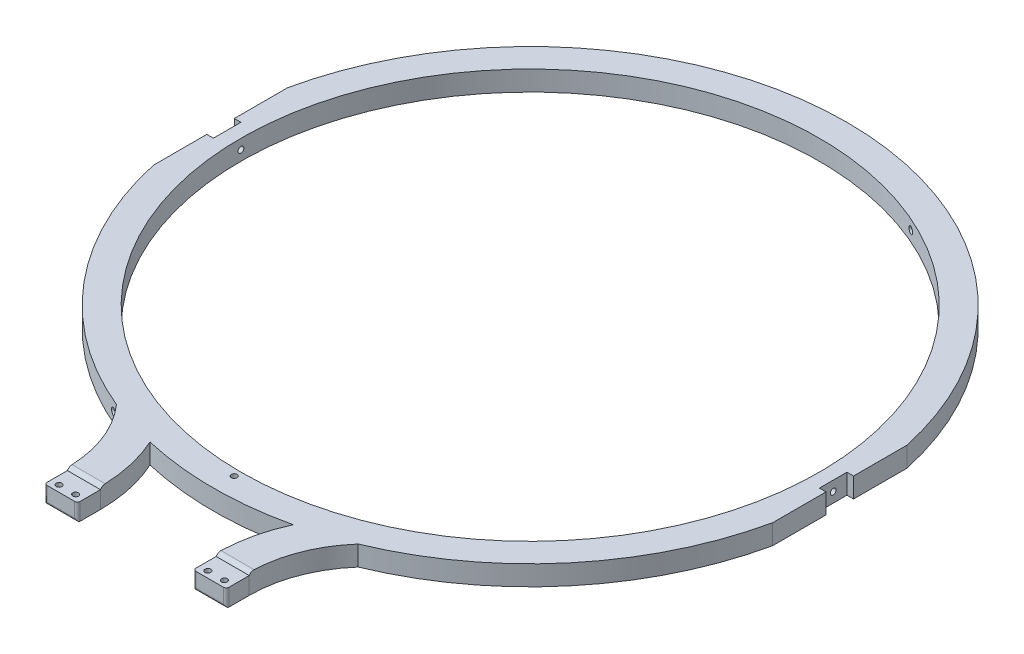
SolidWorks part; units mm, degrees
ref_plane "Front Plane" through (0, 0, 0) normal (0, 0, 1) x (1, 0, 0)
ref_plane "Top Plane" through (0, 0, 0) normal (0, 1, 0) x (1, 0, 0)
ref_plane "Right Plane" through (0, 0, 0) normal (1, 0, 0) x (0, 0, -1)
sketch "Sketch2" plane through (0, 0, 0) normal (0, 1, 0) x (1, 0, 0)
  line L0 (0, -135) -> (0, -115) construction
  line L1 (0, -135) -> (-21, -135) construction
  line L4 (-8.75, -110) -> (8.75, -110) construction
  line L6 (0, -135) -> (21, -135) construction
  line L8 (0, -115) -> (0, -105) construction
  line L11 (-33, -135) -> (-33, -143.35)
  line L12 (-33, -143.35) -> (-21, -143.35)
  line L13 (-21, -135) -> (-21, -143.35)
  line L15 (21, -135) -> (21, -143.35)
  line L16 (21, -143.35) -> (33, -143.35)
  line L17 (33, -135) -> (33, -143.35)
  arc A0 (-26, -112.0223) -> (26, -112.0223) centre (0, 0) ccw
  circle A1 centre (0, 0) radius 105
  arc A5 (-21, -135) -> (-26, -112.0223) centre (-76.2974, -135) ccw
  arc A6 (-33, -135) -> (-43.8788, -106.2998) centre (-76.2974, -135) ccw
  arc A7 (26, -112.0223) -> (21, -135) centre (76.2974, -135) ccw
  arc A8 (43.8788, -106.2998) -> (33, -135) centre (76.2974, -135) ccw
  arc A9 (43.8788, -106.2998) -> (-43.8788, -106.2998) centre (0, 0) ccw
  point P7 (0, -110)
  point P23 (0, -110)
  dimension "D1" = 230
  dimension "D2" = 10
  dimension "D5" = 8.35
  dimension "D6" = 20
  dimension "D3" = 30
  dimension "D4" = 42
  dimension "D7" = 52
  dimension "D8" = 12
extrude "Boss-Extrude1" add sketch "Sketch2" along normal mid plane 7.25
ref_axis "Axis1" through (0, -0.4, 0) along (0, 1, 0)
ref_plane "CenterPlane" through (0, 0, 0) normal (0.3987, 0, -0.9171) x (0, 1, 0)
sketch "Sketch4" plane through (0, 0, 0) normal (0.3987, 0, -0.9171) x (0, 1, 0)
  circle A0 centre (0, 0) radius 1.25
  dimension "D1" = 2.5
extrude "Cut-Extrude1" cut sketch "Sketch4" against normal through all both and the other way through all
ref_plane "Plane2" through (43.8624, 0, -100.8766) normal (0.3987, 0, -0.9171) x (0, 1, 0)
sketch "Sketch6" plane through (43.8624, 0, -100.8766) normal (0.3987, 0, -0.9171) x (0, 1, 0)
  circle A0 centre (0, 0) radius 3.5
  dimension "D1" = 7
sketch "Sketch7" plane through (0, 3.625, 0) normal (0, 1, 0) x (1, 0, 0)
  line L0 (-24, -141) -> (-21, -141) construction
  line L1 (-21, -143.35) -> (-21, -135) construction
  line L2 (24, -141) -> (21, -141) construction
  line L3 (21, -135) -> (21, -143.35) construction
  line L4 (-30, -141) -> (-33, -141) construction
  line L5 (-33, -135) -> (-33, -143.35) construction
  line L6 (30, -141) -> (33, -141) construction
  line L7 (33, -143.35) -> (33, -135) construction
  line L8 (30, -141) -> (24, -141) construction
  line L9 (-24, -141) -> (-30, -141) construction
  circle A0 centre (-30, -141) radius 1.05
  circle A1 centre (-24, -141) radius 1.05
  circle A2 centre (24, -141) radius 1.05
  circle A3 centre (30, -141) radius 1.05
  dimension "D2" = 2.1
  dimension "D1" = 6
  dimension "D4" = 2.35
extrude "Cut-Extrude2" cut sketch "Sketch7" against normal through all
sketch "Sketch9" plane through (0, 0, 0) normal (1, 0, 0) x (0, 0, -1)
  circle A1 centre (0, 0) radius 1.05
  dimension "D1" = 2.1
extrude "Cut-Extrude3" cut sketch "Sketch9" along normal through all both and the other way through all
sketch "Sketch10" plane through (0, 0, 0) normal (0, 1, 0) x (1, 0, 0)
  line L0 (-110, 0) -> (110, 0) construction
  line L1 (-110, 5) -> (-130, 5)
  line L2 (-110, 5) -> (-110, -5)
  line L3 (-110, -5) -> (-130, -5)
  line L4 (-130, 5) -> (-130, -5)
  line L5 (130, 5) -> (110, 5)
  line L6 (130, 5) -> (130, -5)
  line L7 (130, -5) -> (110, -5)
  line L8 (110, 5) -> (110, -5)
  point P10 (0, 0)
  dimension "D1" = 220
  dimension "D2" = 20
  dimension "D3" = 10
extrude "Cut-Extrude4" cut sketch "Sketch10" against normal through all both and the other way through all
sketch "Sketch11" plane through (0, 0, 0) normal (0, 1, 0) x (1, 0, 0)
  line L0 (-112.3913, 0) -> (112.3913, 0) construction
  line L1 (-112.3913, 45) -> (-142.3913, 45)
  line L2 (-112.3913, 45) -> (-112.3913, -45)
  line L3 (-112.3913, -45) -> (-142.3913, -45)
  line L4 (-142.3913, 45) -> (-142.3913, -45)
  line L5 (112.3913, -45) -> (142.3913, -45)
  line L6 (112.3913, -45) -> (112.3913, 45)
  line L7 (112.3913, 45) -> (142.3913, 45)
  line L8 (142.3913, -45) -> (142.3913, 45)
  point P11 (0, 0)
  point P13 (-112.3913, 0)
  dimension "D1" = 2.5
  dimension "D2" = 30
  dimension "D3" = 90
extrude "Cut-Extrude5" cut sketch "Sketch11" against normal through all both and the other way through all
ref_plane "Plane3" through (0, 0, 123.35) normal (0, 0, 1) x (1, 0, 0)
sketch "Sketch12" plane through (0, 3.625, 0) normal (0, 1, 0) x (1, 0, 0)
  circle A2 centre (0, -107.45) radius 1.05
  dimension "D1" = 2.1
  dimension "D2" = 107.45
extrude "Cut-Extrude6" cut sketch "Sketch12" against normal up to surface (7.25 mm away) up to face at (-30, -3.625, 142.05)
fillet "Fillet1" radius 1 8 edges at (21, 0, 143.35) (33, 0, 143.35) (-21, 0, 143.35) (-33, 0, 143.35) (27, -3.625, 143.35) (27, 3.625, 143.35) (-27, -3.625, 143.35) (-27, 3.625, 143.35)
sketch "Sketch13" plane through (0, 3.625, 0) normal (0, 1, 0) x (1, 0, 0)
  line L5 (65, -135) -> (-65, -135)
  line L6 (65, -135) -> (65, -145)
  line L7 (65, -145) -> (-65, -145)
  line L8 (-65, -135) -> (-65, -145)
  point P4 (0, -135)
  dimension "D1" = 130
  dimension "D2" = 10
  dimension "D3" = 135
extrude "Cut-Extrude7" cut sketch "Sketch13" against normal blind 1
fillet "Fillet2" radius 2 2 edges at (27, 3.625, 135) (-27, 3.625, 135)
